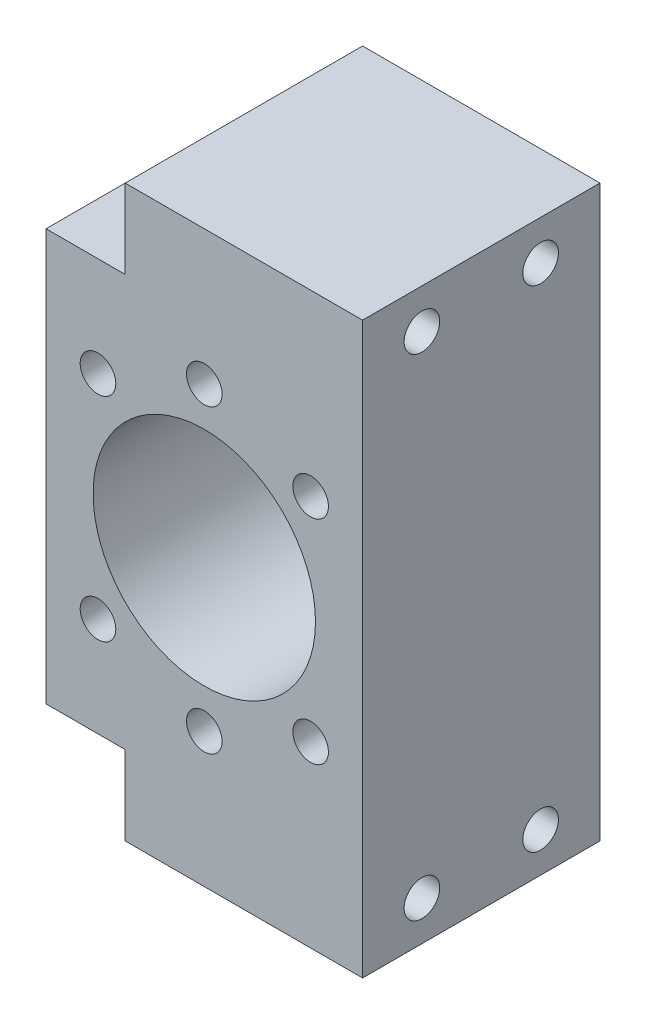
SolidWorks part; units mm, degrees
material "7079 Alloy"
ref_plane "Front" through (0, 0, 0) normal (0, 0, 1) x (1, 0, 0)
ref_plane "Top" through (0, 0, 0) normal (0, 1, 0) x (1, 0, 0)
ref_plane "Right" through (0, 0, 0) normal (1, 0, 0) x (0, 0, -1)
sketch "Sketch2" plane through (0, 0, 10) normal (0, 0, 1) x (1, 0, 0)
  line L0 (20, 0) -> (20, -36)
  line L1 (20, -13.2665) -> (20, 13.2665) construction
  line L2 (20, -36) -> (-20, -36)
  line L3 (-20, -36) -> (-20, 36)
  line L4 (-20, 36) -> (20, 36)
  line L5 (20, 36) -> (20, 0)
  circle A0 centre (13.435, 13.435) radius 2.25
  circle A1 centre (0, 19) radius 2.25
  circle A2 centre (-13.435, 13.435) radius 2.25
  circle A3 centre (-13.435, -13.435) radius 2.25
  circle A4 centre (0, -19) radius 2.25
  circle A5 centre (13.435, -13.435) radius 2.25
  circle A6 centre (0, 0) radius 14.05
extrude "Extrude6" add sketch "Sketch2" along normal blind 30
sketch "Sketch3" plane through (20, 0, 0) normal (1, 0, 0) x (0, 0, -1)
  line L0 (-25, 36) -> (-25, -36)
  line L1 (-40, 36) -> (-10, 36) construction
  line L2 (-40, -36) -> (-10, -36) construction
  line L3 (-40, 36) -> (-25, 36)
  line L4 (-25, 36) -> (-10, 36)
  line L5 (-32.5, 36) -> (-32.5, -36)
  line L6 (-17.5, 36) -> (-17.5, -36)
  line L7 (-32.5, 36) -> (-32.5, 31)
  line L8 (-17.5, 36) -> (-17.5, 31)
  line L9 (-32.5, -36) -> (-32.5, -31)
  line L10 (-17.5, -36) -> (-17.5, -31)
  circle A0 centre (-32.5, -31) radius 2.25
  circle A1 centre (-17.5, -31) radius 2.25
  circle A2 centre (-32.5, 31) radius 2.25
  circle A3 centre (-17.5, 31) radius 2.25
extrude "Cut-Extrude1" cut sketch "Sketch3" against normal blind 30 contours L5 A2 L7 | L7 A2 L5 | L6 A3 L8 | L5 A0 | L5 A0 | L6 A1 | L6 A1
sketch "Sketch4" plane through (-20, 0, 0) normal (-1, 0, 0) x (0, 0, 1)
  line L0 (40, 36) -> (40, -36) construction
  line L1 (10, 36) -> (40, 36)
  line L2 (10, 36) -> (10, 26)
  line L3 (10, 26) -> (40, 26)
  line L4 (40, 36) -> (40, 26)
  line L6 (10, -36) -> (40, -36)
  line L7 (10, -36) -> (10, -26)
  line L8 (10, -26) -> (40, -26)
  line L9 (40, -36) -> (40, -26)
  dimension "D1" = 10
  dimension "D2" = 10
extrude "Cut-Extrude2" cut sketch "Sketch4" against normal blind 10
